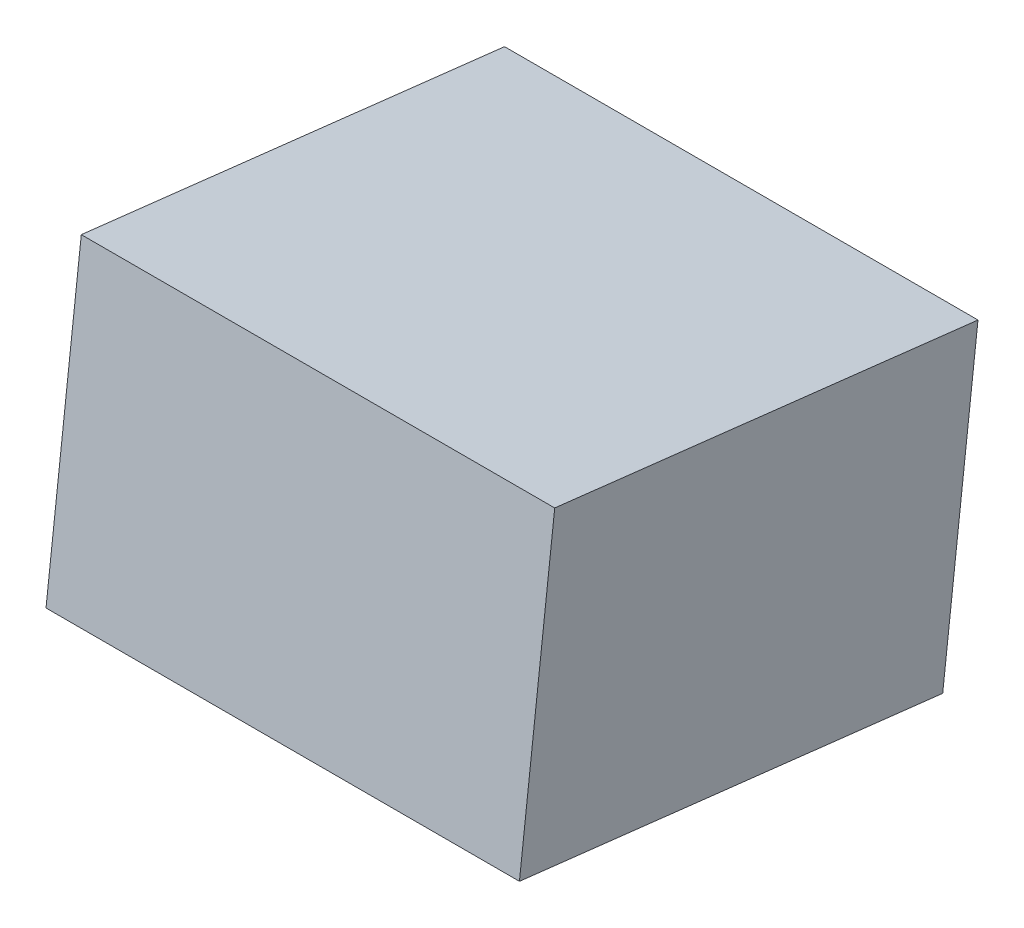
SolidWorks part; units mm, degrees
ref_plane "Front Plane" through (0, 0, 0) normal (0, 0, 1) x (1, 0, 0)
ref_plane "Top Plane" through (0, 0, 0) normal (0, 1, 0) x (1, 0, 0)
ref_plane "Right Plane" through (0, 0, 0) normal (1, 0, 0) x (0, 0, -1)
sketch "Sketch1" plane through (0, 343.9788, -39.7026) normal (0, 0.9934, -0.1147) x (1, 0, 0)
  line L1 (-224.7317, 60.2443) -> (-24.7317, 60.2443)
  line L2 (-224.7317, 60.2443) -> (-224.7317, 240.2443)
  line L3 (-224.7317, 240.2443) -> (-24.7317, 240.2443)
  line L4 (-24.7317, 60.2443) -> (-24.7317, 240.2443)
  line L5 (-224.7317, 60.2443) -> (-24.7317, 240.2443) construction
  line L6 (-224.7317, 240.2443) -> (-24.7317, 60.2443) construction
  point P0 (-124.7317, 150.2443)
  point P6 (0, 0)
  point P7 (116.038, 943.0457)
  point P8 (-147.0345, 965.5294)
  dimension "D1" = 180
  dimension "D2" = 200
extrude "Boss-Extrude1" add sketch "Sketch1" along normal blind 130
